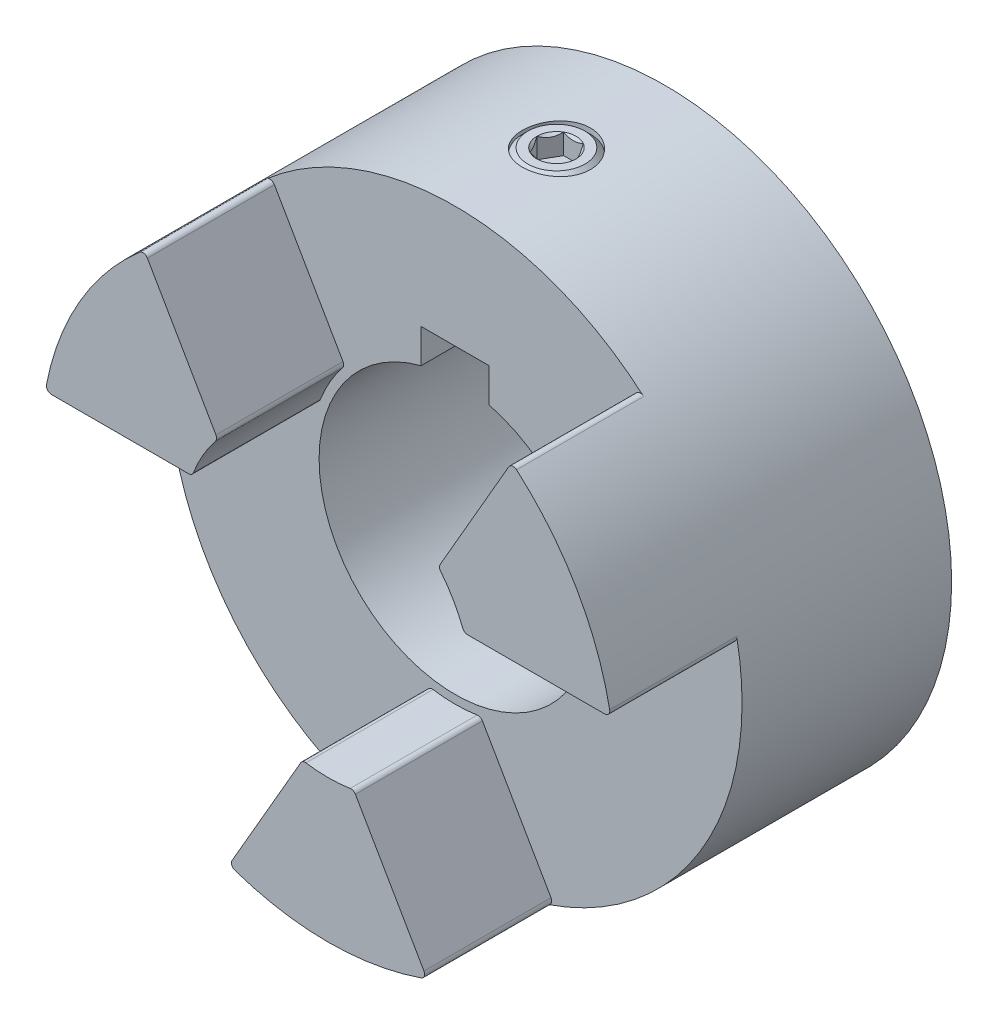
SolidWorks part; units mm, degrees
ref_plane "Front" through (0, 0, 0) normal (0, 0, 1) x (1, 0, 0)
ref_plane "Top" through (0, 0, 0) normal (0, 1, 0) x (1, 0, 0)
ref_plane "Right" through (0, 0, 0) normal (1, 0, 0) x (0, 0, -1)
sketch "Sketch3" plane through (0, 0, 0) normal (1, 0, 0) x (0, 0, -1)
  line L0 (27.3844, 0) -> (-27.3844, 0) construction
  circle A0 centre (0, 0) radius 5.1149 construction
  circle A1 centre (0, 0) radius 12.7 construction
  circle A2 centre (0, 0) radius 26.7891 construction
  point P7 (0, 5.1149)
  point P8 (0, -5.1149)
  point P9 (0, 12.7)
  point P10 (0, -12.7)
  point P11 (0, 26.7891)
  point P12 (0, -26.7891)
  point P13 (6.7469, 0)
  point P14 (-5.1149, 0)
  point P15 (5.1149, 0)
  point P16 (-5.1149, 26.7891)
  point P17 (27.3844, 26.7891)
  point P18 (6.7469, 26.7891)
sketch "Sketch1" plane through (0, 0, 0) normal (0, 0, 1) x (1, 0, 0)
  circle A0 centre (0, 0) radius 26.7891
  circle A1 centre (0, 0) radius 12.7 construction
extrude "Boss-Extrude1" add sketch "Sketch1" against normal up to vertex (27.3844 mm away) from vertex at -6.7469 starting at point (0, 0, -6.7469)
sketch "Sketch10" [suppressed] plane through (0, 0, -3.5719) normal (0, 0, 1) x (1, 0, 0)
  arc A14 (-1.0963, -4.1108) -> (1.0963, -4.1108) centre (0, 0) ccw
  arc A15 (-3.4409, -7.1529) -> (-1.0963, -4.1108) centre (-9.5758, 0) ccw
  arc A19 (1.0963, -4.1108) -> (3.4409, -7.1529) centre (9.5758, 0) ccw
  circle A32 centre (0, 0) radius 7.9375 construction
  arc A33 (-3.4409, -7.1529) -> (3.4409, -7.1529) centre (0, 0) ccw
  point P0 (0, -4.2545)
  point P1 (0, -7.9375)
  dimension "D1" = 3.683
  dimension "D4" = 9.4234
  dimension "D2" = 6.8819
  dimension "D3" = 2.1926
extrude "Boss-Extrude4" [suppressed] add sketch "Sketch10" along normal up to vertex
fillet "Fillet2" [suppressed] radius 0.381
other "Move Face3" [suppressed] parameters "D1"=90
pattern_circular "CirPattern2" [suppressed] count 2 over 360
sketch "Sketch11" [suppressed] plane through (0, 0, -5.9531) normal (0, 0, 1) x (1, 0, 0)
  arc A0 (-1.5825, -7.8835) -> (1.5738, -7.8835) centre (-0.0044, -0.0397) ccw
  arc A1 (-1.5825, -7.8835) -> (-2.9616, -8.354) centre (-1.8681, -9.3029) ccw
  arc A2 (-2.9616, -8.354) -> (-4.9794, -11.8231) centre (5.1535, -15.3956) ccw
  arc A3 (-4.9794, -11.8231) -> (-4.4308, -12.9555) centre (-4.1442, -12.1175) ccw
  arc A4 (-4.4308, -12.9555) -> (4.4176, -12.96) centre (0, 0) ccw
  arc A5 (4.4176, -12.96) -> (4.9692, -11.8231) centre (4.1308, -12.1185) ccw
  arc A6 (4.9692, -11.8231) -> (2.9523, -8.354) centre (-5.1643, -15.3938) ccw
  arc A7 (2.9523, -8.354) -> (1.5738, -7.8835) centre (1.8592, -9.3021) ccw
  circle A8 centre (0, 0) radius 13.6922 construction
  point P18 (-0.007, -13.6922)
  point P19 (-0.0044, -8.0407)
  dimension "D1" = 1.4478
  dimension "D2" = 8.001
  dimension "D3" = 10.7442
  dimension "D4" = 0.889
  dimension "D9" = 5.6515
  dimension "D5" = 5.072
  dimension "D6" = 3.1563
  dimension "D7" = 5.9139
  dimension "D8" = 9.9486
extrude "Boss-Extrude5" [suppressed] add sketch "Sketch11" along normal up to vertex
other "Move Face1" [suppressed] parameters "D1"=90
pattern_circular "CirPattern3" [suppressed] count 2 over 360
sketch "Sketch12" [suppressed] plane through (0, 0, -6.1516) normal (0, 0, 1) x (1, 0, 0)
  line L0 (-5.1097, -10.267) -> (-8.533, -13.6894)
  line L1 (8.533, -13.6894) -> (5.1097, -10.267)
  arc A0 (-2.3442, -9.4968) -> (2.3442, -9.4968) centre (0, 0) ccw
  arc A1 (-2.3442, -9.4968) -> (-5.1097, -10.267) centre (-3.0443, -12.333) ccw
  arc A2 (-8.533, -13.6894) -> (-8.3299, -15.1215) centre (-7.8934, -14.3292) ccw
  arc A3 (-8.3299, -15.1215) -> (8.3299, -15.1215) centre (0, 0) ccw
  arc A4 (8.3299, -15.1215) -> (8.533, -13.6894) centre (7.8934, -14.3292) ccw
  arc A5 (5.1097, -10.267) -> (2.3442, -9.4968) centre (3.0443, -12.333) ccw
  circle A6 centre (0, 0) radius 17.2641 construction
  point P16 (0, -9.7819)
  point P17 (0, -17.2641)
  dimension "D1" = 7.4822
  dimension "D2" = 10.2193
  dimension "D3" = 4.6884
  dimension "D4" = 17.066
  dimension "D5" = 16.6598
extrude "Boss-Extrude6" [suppressed] add sketch "Sketch12" along normal up to vertex
other "Move Face2" [suppressed] parameters "D1"=90
pattern_circular "CirPattern4" [suppressed] count 2 over 360
sketch "Sketch2" plane through (0, 0, -6.7469) normal (0, 0, 1) x (1, 0, 0)
  line L0 (-9.2385, -25.1456) -> (-2.385, -13.2749)
  line L2 (2.385, -13.2749) -> (9.2385, -25.1456)
  circle A0 centre (0, 0) radius 26.7891 construction
  arc A1 (-9.2385, -25.1456) -> (9.2385, -25.1456) centre (0, 0) ccw
  arc A2 (-2.385, -13.2749) -> (2.385, -13.2749) centre (0, 0) ccw
  circle A3 centre (0, 0) radius 4.572 construction
  dimension "D1" = 60
extrude "Boss-Extrude2" add sketch "Sketch2" along normal up to vertex (21.4313 mm away)
fillet "Fillet1" radius 0.477 4 edges at (2.385, -13.2749, -0.816) (-2.385, -13.2749, -0.816)
pattern_circular "CirPattern1" count 3 over 360 about axis through (0, 0, 0) along (0, 0, 1) of "Boss-Extrude2", "Fillet1"
sketch "Sketch15" plane through (0, 0, 0) normal (0, 0, 1) x (1, 0, 0)
  circle A0 centre (0, 0) radius 12.7
extrude "Cut-Extrude5" cut sketch "Sketch15" against normal through all and the other way through all
chamfer "Chamfer1" distance 1.0716 angle 56 2 edges at (26.7891, 0, -27.3844) (12.7, 0, -27.3844)
sketch "Sketch4" plane through (0, 0, 0) normal (0, 0, 1) x (1, 0, 0)
  line L1 (-3.175, 15.4717) -> (3.175, 15.4717)
  line L2 (-3.175, 15.4717) -> (-3.175, 12.2967)
  line L4 (3.175, 15.4717) -> (3.175, 12.2967)
  arc A1 (3.175, 12.2967) -> (-3.175, 12.2967) centre (0, 0) ccw
  circle A2 centre (0, 0) radius 12.7 construction
  dimension "Keyway Ht" = 3.175
  dimension "Keyway Wd" = 6.35
extrude "Cut-Extrude1" cut sketch "Sketch4" against normal through all and the other way through all
sketch "Sketch5" plane through (0, 0, 0) normal (0, 1, 0) x (1, 0, 0)
  line L1 (0, -46.4939) -> (0, 46.4939) construction
  circle A0 centre (0, 16.2084) radius 3.175
extrude "Cut-Extrude2" cut sketch "Sketch5" along normal through all
ref_plane "Plane1" through (0, 26.7891, 0) normal (0, 1, 0) x (-1, 0, 0)
sketch "Sketch6" plane through (0, 26.7891, 0) normal (0, 1, 0) x (-1, 0, 0)
  circle A1 centre (0, -16.2084) radius 3.175
  circle A2 centre (0, -16.2084) radius 3.175
  dimension "D1" = 0
extrude "Boss-Extrude3" add sketch "Sketch6" against normal blind 7.9375 separate body
sketch "Sketch8" plane through (0, 26.7891, 0) normal (0, 1, 0) x (1, 0, 0)
  line L1 (0.9165, 14.6209) -> (1.8331, 16.2084)
  line L2 (1.8331, 16.2084) -> (0.9165, 17.7959)
  line L3 (0.9165, 17.7959) -> (-0.9165, 17.7959)
  line L4 (-0.9165, 17.7959) -> (-1.8331, 16.2084)
  line L5 (-1.8331, 16.2084) -> (-0.9165, 14.6209)
  line L6 (-0.9165, 14.6209) -> (0.9165, 14.6209)
  circle A0 centre (0, 16.2084) radius 1.5875 construction
  dimension "D1" = 3.175
extrude "Cut-Extrude3" cut sketch "Sketch8" against normal blind 1.905
sketch "Sketch9" plane through (0, 26.7891, 0) normal (0, 1, 0) x (1, 0, 0)
  circle A0 centre (0, 16.2084) radius 1.8331
extrude "Cut-Extrude4" cut sketch "Sketch9" against normal through all draft 45
chamfer "Chamfer3" distance 0.508 angle 45 1 edges at (0, 26.7891, -13.0334)
chamfer "Chamfer4" distance 1.0795 angle 45 1 edges at (0, 18.8516, -13.0334)
sketch "Sketch16" [suppressed] plane through (0, 0, -61.9125) normal (0, 0, -1) x (-1, 0, 0)
  circle A0 centre (0, 0) radius 50.8
  dimension "D1" = 101.6
extrude "Cut-Extrude6" [suppressed] cut sketch "Sketch16" against normal blind 30.3022 flip side to cut
chamfer "Chamfer5" [suppressed] distance 1.778 angle 56
fillet "Fillet3" [suppressed] radius 1.27
move or copy body "Body-Move/Copy1" [suppressed] bodies to move or copy 115 copy no translate (0, -6.35, 0)
sketch "Sketch17" [suppressed] plane through (0, 0, -67.8656) normal (0, 0, -1) x (-1, 0, 0)
  circle A0 centre (0, 0) radius 53.975
  dimension "D1" = 107.95
extrude "Cut-Extrude7" [suppressed] cut sketch "Sketch17" against normal blind 36.576 flip side to cut
move or copy body "Body-Move/Copy2" [suppressed] bodies to move or copy 115 copy no translate (0, -9.525, 0)
fillet "Fillet4" [suppressed] radius 2.54
fillet "Fillet5" [suppressed] radius 1.27
equation "\"D1@Chamfer1\" = \"OD@Sketch3\" * .02"
equation "\"D1@Fillet1\" = \"D4@Sketch2\" * .1"
equation "\"D1@Sketch8\" = \"Screw Dia@Sketch5\" * .5"
equation "\"D1@Cut-Extrude3\" = \"Screw Dia@Sketch5\" * .3"
equation "\"D1@Chamfer3\" = \"Screw Dia@Sketch5\" * .08"
equation "\"D1@Chamfer4\" = \"Screw Dia@Sketch5\" * .17"
